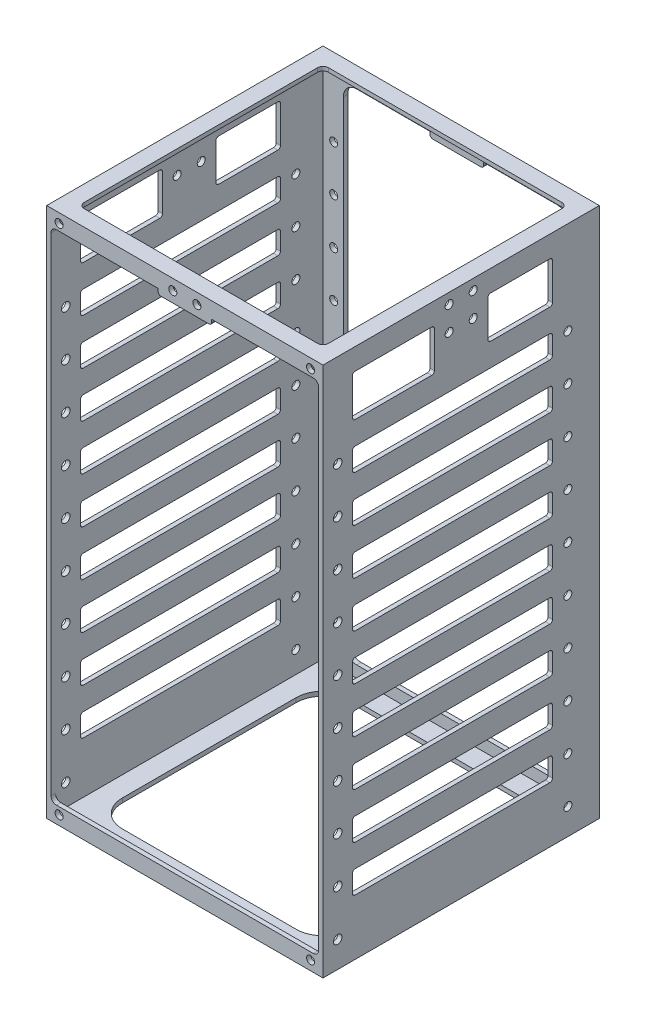
SolidWorks part; units mm, degrees
material "5052-H32"
ref_plane "Front Plane" through (0, 0, 0) normal (0, 0, 1) x (1, 0, 0)
ref_plane "Top Plane" through (0, 0, 0) normal (0, 1, 0) x (1, 0, 0)
ref_plane "Right Plane" through (0, 0, 0) normal (1, 0, 0) x (0, 0, -1)
sketch "Sketch1" plane through (0, 0, 0) normal (0, 1, 0) x (1, 0, 0)
  line L1 (-51.63, -51.63) -> (51.63, -51.63)
  line L2 (-51.63, -51.63) -> (-51.63, 51.63)
  line L3 (-51.63, 51.63) -> (51.63, 51.63)
  line L4 (51.63, -51.63) -> (51.63, 51.63)
  line L5 (-51.63, -51.63) -> (51.63, 51.63) construction
  line L6 (-51.63, 51.63) -> (51.63, -51.63) construction
  line L7 (-32.5, -42.5) -> (32.5, -42.5)
  line L8 (-42.5, -32.5) -> (-42.5, 32.5)
  line L9 (-32.5, 42.5) -> (32.5, 42.5)
  line L10 (42.5, -32.5) -> (42.5, 32.5)
  line L11 (-42.5, -42.5) -> (42.5, 42.5) construction
  line L12 (-42.5, 42.5) -> (42.5, -42.5) construction
  arc A0 (32.5, -42.5) -> (42.5, -32.5) centre (32.5, -32.5) ccw
  arc A1 (32.5, 42.5) -> (42.5, 32.5) centre (32.5, 32.5) cw
  arc A2 (-42.5, 32.5) -> (-32.5, 42.5) centre (-32.5, 32.5) cw
  arc A3 (-32.5, -42.5) -> (-42.5, -32.5) centre (-32.5, -32.5) cw
  point P0 (0, 0)
  point P6 (0, 0)
  dimension "D3" = 10
  dimension "D1" = 103.26
  dimension "D2" = 42.5
extrude "Boss-Extrude2" add sketch "Sketch1" along normal blind 1.63 contours A3 L7 A0 L10 A1 L9 A2 L8 | L2 L1 L4 L3 region at (0, 0, 0)
sketch "Sketch3" plane through (0, 1.63, 0) normal (0, 1, 0) x (1, 0, 0)
  line L1 (-51.63, -51.63) -> (51.63, -51.63)
  line L2 (-51.63, -51.63) -> (-51.63, 51.63)
  line L3 (-51.63, 51.63) -> (51.63, 51.63)
  line L4 (51.63, -51.63) -> (51.63, 51.63)
  line L5 (-51.63, -51.63) -> (51.63, 51.63) construction
  line L6 (-51.63, 51.63) -> (51.63, -51.63) construction
  line L7 (-50, -50) -> (50, -50)
  line L8 (-50, -50) -> (-50, 50)
  line L9 (-50, 50) -> (50, 50)
  line L10 (50, -50) -> (50, 50)
  line L11 (-50, -50) -> (50, 50) construction
  line L12 (-50, 50) -> (50, -50) construction
  point P0 (0, 0)
  point P7 (0, 0)
  dimension "D1" = 100
extrude "Boss-Extrude3" add sketch "Sketch3" along normal blind 196.74 contours L8 L7 L10 L9 | L2 L3 L4 L1
sketch "Sketch4" plane through (0, 0, -51.63) normal (0, 0, 1) x (1, 0, 0)
  line L0 (-51.63, 0) -> (51.63, 0) construction
  line L1 (-37.38, 6) -> (37.38, 6)
  line L2 (-42.38, 11) -> (-42.38, 187.37)
  line L3 (-37.38, 192.37) -> (37.38, 192.37)
  line L4 (42.38, 11) -> (42.38, 187.37)
  line L5 (-42.38, 6) -> (42.38, 192.37) construction
  line L6 (-42.38, 192.37) -> (42.38, 6) construction
  line L7 (51.63, 198.37) -> (51.63, 0) construction
  line L8 (-50, 198.37) -> (50, 198.37) construction
  line L9 (-51.63, 198.37) -> (-51.63, 0) construction
  arc A0 (-37.38, 6) -> (-42.38, 11) centre (-37.38, 11) cw
  arc A1 (37.38, 6) -> (42.38, 11) centre (37.38, 11) ccw
  arc A2 (37.38, 192.37) -> (42.38, 187.37) centre (37.38, 187.37) cw
  arc A3 (-42.38, 187.37) -> (-37.38, 192.37) centre (-37.38, 187.37) cw
  point P0 (0, 99.185)
  dimension "D5" = 5
  dimension "D1" = 6
  dimension "D2" = 9.25
  dimension "D3" = 6
  dimension "D4" = 9.25
extrude "Cut-Extrude1" cut sketch "Sketch4" along normal up to surface (1.63 mm away) up to face at (0, 100, -50)
sketch "Sketch5" plane through (0, 0, 51.63) normal (0, 0, 1) x (1, 0, 0)
  line L0 (-51.63, 198.37) -> (51.63, 198.37) construction
  line L1 (-48, 6.13) -> (48, 6.13)
  line L2 (-50, 8.13) -> (-50, 190.37)
  line L3 (-48, 192.37) -> (48, 192.37)
  line L4 (50, 8.13) -> (50, 190.37)
  line L5 (-50, 6.13) -> (50, 192.37) construction
  line L6 (-50, 192.37) -> (50, 6.13) construction
  line L7 (-51.63, 1.63) -> (51.63, 1.63) construction
  line L8 (-51.63, 198.37) -> (-51.63, 0) construction
  line L9 (51.63, 198.37) -> (51.63, 0) construction
  arc A0 (48, 6.13) -> (50, 8.13) centre (48, 8.13) ccw
  arc A1 (-48, 6.13) -> (-50, 8.13) centre (-48, 8.13) cw
  arc A2 (48, 192.37) -> (50, 190.37) centre (48, 190.37) cw
  arc A3 (-50, 190.37) -> (-48, 192.37) centre (-48, 190.37) cw
  point P0 (0, 99.25)
  dimension "D1" = 6
  dimension "D5" = 2
  dimension "D2" = 4.5
  dimension "D3" = 1.63
  dimension "D4" = 1.63
sketch "Sketch6" plane through (51.63, 0, 0) normal (1, 0, 0) x (0, 0, -1)
  line L0 (-51.63, 6.13) -> (-51.63, 192.37) construction
  line L2 (-51.63, 0) -> (51.63, 0) construction
  circle A0 centre (-46.13, 9.75) radius 1.6
  circle A1 centre (39.87, 9.75) radius 1.5
  circle A2 centre (-46.13, 26.85) radius 1.6
  circle A3 centre (39.87, 26.85) radius 1.5
  circle A4 centre (-46.13, 43.95) radius 1.6
  circle A5 centre (39.87, 43.95) radius 1.5
  circle A6 centre (-46.13, 61.05) radius 1.6
  circle A7 centre (39.87, 61.05) radius 1.5
  circle A8 centre (-46.13, 78.15) radius 1.6
  circle A9 centre (39.87, 78.15) radius 1.5
  circle A10 centre (-46.13, 95.25) radius 1.6
  circle A11 centre (39.87, 95.25) radius 1.5
  circle A12 centre (-46.13, 112.35) radius 1.6
  circle A13 centre (39.87, 112.35) radius 1.5
  circle A14 centre (-46.13, 129.45) radius 1.6
  circle A15 centre (39.87, 129.45) radius 1.5
  circle A16 centre (-46.13, 146.55) radius 1.6
  circle A17 centre (39.87, 146.55) radius 1.5
  circle A18 centre (-46.13, 163.65) radius 1.6
  circle A19 centre (39.87, 163.65) radius 1.5
  dimension "D4" = 3
  dimension "D5" = 3.2
  dimension "D1" = 5.5
  dimension "D2" = 86
  dimension "D3" = 9.75
  dimension "D7" = 17.1
  dimension "D9" = 17.1
  dimension "D6" = 9
  dimension "D8" = 2
extrude "Cut-Extrude2" cut sketch "Sketch6" against normal through all
extrude "Cut-Extrude3" cut sketch "Sketch5" against normal up to surface (1.63 mm away) up to face at (0, 100, 50)
sketch "Sketch7" plane through (51.63, 0, 0) normal (1, 0, 0) x (0, 0, -1)
  line L0 (-40.63, 38.95) -> (-40.63, 45.45)
  line L1 (-39.63, 20.85) -> (33.12, 20.85)
  line L2 (-40.63, 21.85) -> (-40.63, 28.35)
  line L3 (-39.63, 29.35) -> (33.12, 29.35)
  line L4 (34.12, 21.85) -> (34.12, 28.35)
  line L5 (-40.63, 20.85) -> (34.12, 29.35) construction
  line L6 (-40.63, 29.35) -> (34.12, 20.85) construction
  line L7 (-40.63, 158.65) -> (-40.63, 165.15)
  line L8 (-39.63, 37.95) -> (33.12, 37.95)
  line L9 (34.12, 38.95) -> (34.12, 45.45)
  line L10 (-39.63, 46.45) -> (33.12, 46.45)
  line L11 (-40.63, 56.05) -> (-40.63, 62.55)
  line L12 (-39.63, 55.05) -> (33.12, 55.05)
  line L13 (34.12, 56.05) -> (34.12, 62.55)
  line L14 (-39.63, 63.55) -> (33.12, 63.55)
  line L15 (-40.63, 73.15) -> (-40.63, 79.65)
  line L16 (-39.63, 72.15) -> (33.12, 72.15)
  line L17 (34.12, 73.15) -> (34.12, 79.65)
  line L18 (-39.63, 80.65) -> (33.12, 80.65)
  line L19 (-40.63, 90.25) -> (-40.63, 96.75)
  line L20 (-39.63, 89.25) -> (33.12, 89.25)
  line L21 (34.12, 90.25) -> (34.12, 96.75)
  line L22 (-39.63, 97.75) -> (33.12, 97.75)
  line L23 (-40.63, 107.35) -> (-40.63, 113.85)
  line L24 (-39.63, 106.35) -> (33.12, 106.35)
  line L25 (34.12, 107.35) -> (34.12, 113.85)
  line L26 (-39.63, 114.85) -> (33.12, 114.85)
  line L27 (-40.63, 124.45) -> (-40.63, 130.95)
  line L28 (-39.63, 123.45) -> (33.12, 123.45)
  line L29 (34.12, 124.45) -> (34.12, 130.95)
  line L30 (-39.63, 131.95) -> (33.12, 131.95)
  line L31 (-40.63, 141.55) -> (-40.63, 148.05)
  line L32 (-39.63, 140.55) -> (33.12, 140.55)
  line L33 (34.12, 141.55) -> (34.12, 148.05)
  line L34 (-39.63, 149.05) -> (33.12, 149.05)
  line L35 (-39.63, 157.65) -> (33.12, 157.65)
  line L36 (34.12, 158.65) -> (34.12, 165.15)
  line L37 (-39.63, 166.15) -> (33.12, 166.15)
  line L38 (-40.63, 141.55) -> (-40.63, 158.65) construction
  circle A0 centre (-46.13, 9.75) radius 1.6 construction
  arc A1 (33.12, 29.35) -> (34.12, 28.35) centre (33.12, 28.35) cw
  arc A2 (33.12, 20.85) -> (34.12, 21.85) centre (33.12, 21.85) ccw
  arc A3 (-39.63, 20.85) -> (-40.63, 21.85) centre (-39.63, 21.85) cw
  arc A4 (-40.63, 28.35) -> (-39.63, 29.35) centre (-39.63, 28.35) cw
  arc A5 (-40.63, 45.45) -> (-39.63, 46.45) centre (-39.63, 45.45) cw
  arc A6 (-39.63, 37.95) -> (-40.63, 38.95) centre (-39.63, 38.95) cw
  arc A7 (33.12, 37.95) -> (34.12, 38.95) centre (33.12, 38.95) ccw
  arc A8 (33.12, 46.45) -> (34.12, 45.45) centre (33.12, 45.45) cw
  arc A9 (-40.63, 62.55) -> (-39.63, 63.55) centre (-39.63, 62.55) cw
  arc A10 (-39.63, 55.05) -> (-40.63, 56.05) centre (-39.63, 56.05) cw
  arc A11 (33.12, 55.05) -> (34.12, 56.05) centre (33.12, 56.05) ccw
  arc A12 (33.12, 63.55) -> (34.12, 62.55) centre (33.12, 62.55) cw
  arc A13 (-40.63, 79.65) -> (-39.63, 80.65) centre (-39.63, 79.65) cw
  arc A14 (-39.63, 72.15) -> (-40.63, 73.15) centre (-39.63, 73.15) cw
  arc A15 (33.12, 72.15) -> (34.12, 73.15) centre (33.12, 73.15) ccw
  arc A16 (33.12, 80.65) -> (34.12, 79.65) centre (33.12, 79.65) cw
  arc A17 (-40.63, 96.75) -> (-39.63, 97.75) centre (-39.63, 96.75) cw
  arc A18 (-39.63, 89.25) -> (-40.63, 90.25) centre (-39.63, 90.25) cw
  arc A19 (33.12, 89.25) -> (34.12, 90.25) centre (33.12, 90.25) ccw
  arc A20 (33.12, 97.75) -> (34.12, 96.75) centre (33.12, 96.75) cw
  arc A21 (-40.63, 113.85) -> (-39.63, 114.85) centre (-39.63, 113.85) cw
  arc A22 (-39.63, 106.35) -> (-40.63, 107.35) centre (-39.63, 107.35) cw
  arc A23 (33.12, 106.35) -> (34.12, 107.35) centre (33.12, 107.35) ccw
  arc A24 (33.12, 114.85) -> (34.12, 113.85) centre (33.12, 113.85) cw
  arc A25 (-40.63, 130.95) -> (-39.63, 131.95) centre (-39.63, 130.95) cw
  arc A26 (-39.63, 123.45) -> (-40.63, 124.45) centre (-39.63, 124.45) cw
  arc A27 (33.12, 123.45) -> (34.12, 124.45) centre (33.12, 124.45) ccw
  arc A28 (33.12, 131.95) -> (34.12, 130.95) centre (33.12, 130.95) cw
  arc A29 (-40.63, 148.05) -> (-39.63, 149.05) centre (-39.63, 148.05) cw
  arc A30 (-39.63, 140.55) -> (-40.63, 141.55) centre (-39.63, 141.55) cw
  arc A31 (33.12, 140.55) -> (34.12, 141.55) centre (33.12, 141.55) ccw
  arc A32 (33.12, 149.05) -> (34.12, 148.05) centre (33.12, 148.05) cw
  arc A33 (-40.63, 165.15) -> (-39.63, 166.15) centre (-39.63, 165.15) cw
  arc A34 (-39.63, 157.65) -> (-40.63, 158.65) centre (-39.63, 158.65) cw
  circle A35 centre (39.87, 9.75) radius 1.5 construction
  arc A36 (33.12, 157.65) -> (34.12, 158.65) centre (33.12, 158.65) ccw
  arc A37 (33.12, 166.15) -> (34.12, 165.15) centre (33.12, 165.15) cw
  point P0 (-3.255, 25.1)
  dimension "D5" = 1
  dimension "D3" = 5.75
  dimension "D1" = 8.5
  dimension "D2" = 11.1
  dimension "D4" = 5.5
  dimension "D7" = 8.6
  dimension "D9" = 8.6
  dimension "D6" = 8
  dimension "D8" = 2
extrude "Cut-Extrude4" cut sketch "Sketch7" against normal through all
sketch "Sketch8" plane through (51.63, 0, 0) normal (1, 0, 0) x (0, 0, -1)
  line L7 (-51.63, 198.37) -> (51.63, 198.37) construction
  line L15 (-39.63, 190.37) -> (33.12, 190.37)
  line L16 (-40.63, 189.37) -> (-40.63, 175.75)
  line L17 (-39.63, 174.75) -> (33.12, 174.75)
  line L18 (34.12, 189.37) -> (34.12, 175.75)
  line L19 (33.12, 166.15) -> (-39.63, 166.15) construction
  arc A15 (33.12, 190.37) -> (34.12, 189.37) centre (33.12, 189.37) cw
  arc A16 (33.12, 174.75) -> (34.12, 175.75) centre (33.12, 175.75) ccw
  arc A17 (-40.63, 175.75) -> (-39.63, 174.75) centre (-39.63, 175.75) ccw
  arc A18 (-39.63, 190.37) -> (-40.63, 189.37) centre (-39.63, 189.37) ccw
  circle A19 centre (-46.13, 163.65) radius 1.6 construction
  circle A20 centre (39.87, 163.65) radius 1.5 construction
  point P0 (-2.625, 162.85)
  dimension "D6" = 1
  dimension "D2" = 8.6
  dimension "D8" = 8
  dimension "D9" = 5.5
  dimension "D10" = 5.75
extrude "Cut-Extrude5" cut sketch "Sketch8" against normal through all
sketch "Sketch15" plane through (51.63, 0, 0) normal (1, 0, 0) x (0, 0, -1)
  line L0 (-50, 198.37) -> (-50, 190.37) construction
  line L7 (33.12, 190.37) -> (-39.63, 190.37) construction
  line L8 (-10, 190.37) -> (10, 190.37)
  line L9 (-10, 190.37) -> (-10, 174.75)
  line L10 (-10, 174.75) -> (10, 174.75)
  line L11 (10, 190.37) -> (10, 174.75)
  line L12 (-39.63, 174.75) -> (33.12, 174.75) construction
  dimension "D1" = 20
  dimension "D2" = 40
extrude "Boss-Extrude4" add sketch "Sketch15" against normal up to surface (1.63 mm away) up to face at (50, 182.56, 3.255)
sketch "Sketch16" plane through (-51.63, 0, 0) normal (-1, 0, 0) x (0, 0, 1)
  line L7 (-10, 190.37) -> (10, 190.37)
  line L8 (-10, 190.37) -> (-10, 174.75)
  line L9 (-10, 174.75) -> (10, 174.75)
  line L10 (10, 190.37) -> (10, 174.75)
extrude "Boss-Extrude5" add sketch "Sketch16" against normal up to surface (1.63 mm away) up to face at (-50, 182.56, 3.255)
sketch "Sketch9" plane through (51.63, 0, 0) normal (1, 0, 0) x (0, 0, -1)
  line L0 (-51.63, 198.37) -> (51.63, 198.37) construction
  line L2 (-11.0428, 189.87) -> (9.2919, 189.87) construction
  line L3 (-50, 198.37) -> (-50, 190.37) construction
  circle A0 centre (-4.5, 194.37) radius 1.5
  circle A1 centre (4.5, 194.37) radius 1.5
  circle A2 centre (4.5, 185.37) radius 1.5
  circle A3 centre (-4.5, 185.37) radius 1.5
  dimension "D1" = 3
  dimension "D3" = 9
  dimension "D5" = 3
  dimension "D2" = 4
  dimension "D4" = 45.5
  dimension "D6" = 4.5
extrude "Cut-Extrude6" cut sketch "Sketch9" against normal through all
fillet "Fillet1" radius 1 8 edges at (-50.815, 174.75, 10) (-50.815, 190.37, 10) (-50.815, 190.37, -10) (-50.815, 174.75, -10) (50.815, 190.37, 10) (50.815, 174.75, 10) (50.815, 174.75, -10) (50.815, 190.37, -10)
sketch "Sketch18" plane through (0, 0, -51.63) normal (0, 0, -1) x (-1, 0, 0)
  line L0 (-37.38, 192.37) -> (37.38, 192.37) construction
  line L1 (-10, 192.37) -> (10, 192.37)
  line L2 (-10, 192.37) -> (-10, 191.37)
  line L3 (-9, 190.37) -> (9, 190.37)
  line L4 (10, 192.37) -> (10, 191.37)
  line L6 (-50, 198.37) -> (-50, 1.63) construction
  arc A0 (9, 190.37) -> (10, 191.37) centre (9, 191.37) ccw
  arc A1 (-10, 191.37) -> (-9, 190.37) centre (-9, 191.37) ccw
  point P4 (-10, 191.87)
  dimension "D3" = 1
  dimension "D1" = 2
  dimension "D2" = 20
  dimension "D4" = 40
extrude "Boss-Extrude7" add sketch "Sketch18" against normal up to surface (1.63 mm away) up to face at (0, 99.185, -50)
sketch "Sketch17" plane through (0, 0, 51.63) normal (0, 0, 1) x (1, 0, 0)
  line L0 (48, 192.37) -> (-48, 192.37) construction
  line L1 (-10, 192.37) -> (10, 192.37)
  line L2 (-10, 192.37) -> (-10, 191.37)
  line L3 (-9, 190.37) -> (9, 190.37)
  line L4 (10, 192.37) -> (10, 191.37)
  line L5 (-50, 198.37) -> (-50, 190.37) construction
  arc A0 (9, 190.37) -> (10, 191.37) centre (9, 191.37) ccw
  arc A1 (-10, 191.37) -> (-9, 190.37) centre (-9, 191.37) ccw
  dimension "D4" = 1
  dimension "D1" = 20
  dimension "D2" = 40
  dimension "D3" = 2
extrude "Boss-Extrude6" add sketch "Sketch17" against normal up to surface (1.63 mm away) up to face at (0, 193.8414, 50)
sketch "Sketch19" plane through (0, 0, 51.63) normal (0, 0, 1) x (1, 0, 0)
  line L0 (0, 198.37) -> (0, 190.37) construction
  line L1 (-9, 190.37) -> (9, 190.37) construction
  line L3 (-51.63, 198.37) -> (51.63, 198.37) construction
  circle A0 centre (-4.5, 194.37) radius 1.5
  circle A1 centre (4.5, 194.37) radius 1.5
  dimension "D1" = 3
  dimension "D2" = 4
  dimension "D3" = 4.5
extrude "Cut-Extrude7" cut sketch "Sketch19" against normal through all
sketch "Sketch20" plane through (0, 0, 51.63) normal (0, 0, 1) x (1, 0, 0)
  line L1 (-51.63, 0) -> (51.63, 0) construction
  line L2 (0, 198.37) -> (0, 0) construction
  line L3 (-51.63, 198.37) -> (51.63, 198.37) construction
  line L4 (-50, 198.37) -> (-50, 190.37) construction
  line L5 (-50, 8.13) -> (-50, 1.63) construction
  circle A0 centre (-46.98, 3.5) radius 1.5
  circle A1 centre (-46.98, 194.87) radius 1.5
  circle A2 centre (46.98, 3.5) radius 1.5
  circle A3 centre (46.98, 194.87) radius 1.5
  dimension "D1" = 3
  dimension "D4" = 3
  dimension "D2" = 3.02
  dimension "D3" = 3.5
  dimension "D5" = 3.02
  dimension "D6" = 3.5
extrude "Cut-Extrude8" cut sketch "Sketch20" against normal up to surface (1.63 mm away) up to face at (-6, 194.37, 50)
sketch "Sketch23" plane through (0, 0, -51.63) normal (0, 0, -1) x (-1, 0, 0)
  line L0 (-51.63, 198.37) -> (-51.63, 0) construction
  line L1 (51.63, 0) -> (-51.63, 0) construction
  line L2 (0, 198.37) -> (0, 0) construction
  line L3 (51.63, 198.37) -> (-51.63, 198.37) construction
  circle A0 centre (-46, 17.05) radius 1.5
  circle A2 centre (-46, 34.15) radius 1.5
  circle A3 centre (-46, 51.25) radius 1.5
  circle A4 centre (-46, 68.35) radius 1.5
  circle A5 centre (-46, 85.45) radius 1.5
  circle A6 centre (-46, 102.55) radius 1.5
  circle A7 centre (-46, 119.65) radius 1.5
  circle A8 centre (-46, 136.75) radius 1.5
  circle A9 centre (-46, 153.85) radius 1.5
  circle A10 centre (-46, 170.95) radius 1.5
  circle A11 centre (46, 170.95) radius 1.5
  circle A12 centre (46, 153.85) radius 1.5
  circle A13 centre (46, 136.75) radius 1.5
  circle A14 centre (46, 119.65) radius 1.5
  circle A15 centre (46, 102.55) radius 1.5
  circle A16 centre (46, 85.45) radius 1.5
  circle A17 centre (46, 68.35) radius 1.5
  circle A18 centre (46, 51.25) radius 1.5
  circle A19 centre (46, 34.15) radius 1.5
  circle A20 centre (46, 17.05) radius 1.5
  dimension "D1" = 3
  dimension "D2" = 5.63
  dimension "D3" = 17.05
  dimension "D5" = 17.1
  dimension "D4" = 10
extrude "Cut-Extrude10" cut sketch "Sketch23" against normal up to surface (1.63 mm away) up to face at (-6, 194.37, -50)
sketch "Sketch25" plane through (0, 198.37, 0) normal (0, 1, 0) x (1, 0, 0)
  line L1 (-50, -50) -> (50, -50)
  line L2 (-50, -50) -> (-50, 50)
  line L3 (-50, 50) -> (50, 50)
  line L4 (50, -50) -> (50, 50)
  line L5 (-50, -50) -> (50, 50) construction
  line L6 (-50, 50) -> (50, -50) construction
  point P0 (0, 0)
extrude "Boss-Extrude8" add sketch "Sketch25" against normal blind 1.5
sketch "Sketch26" plane through (0, 198.37, 0) normal (0, 1, 0) x (1, 0, 0)
  line L0 (-51.63, -51.63) -> (-51.63, 51.63) construction
  line L1 (-43.63, -45.63) -> (43.63, -45.63)
  line L2 (-45.63, -43.63) -> (-45.63, 43.63)
  line L3 (-43.63, 45.63) -> (43.63, 45.63)
  line L4 (45.63, -43.63) -> (45.63, 43.63)
  line L5 (-45.63, -45.63) -> (45.63, 45.63) construction
  line L6 (-45.63, 45.63) -> (45.63, -45.63) construction
  arc A0 (-45.63, 43.63) -> (-43.63, 45.63) centre (-43.63, 43.63) cw
  arc A1 (43.63, 45.63) -> (45.63, 43.63) centre (43.63, 43.63) cw
  arc A2 (43.63, -45.63) -> (45.63, -43.63) centre (43.63, -43.63) ccw
  arc A3 (-43.63, -45.63) -> (-45.63, -43.63) centre (-43.63, -43.63) cw
  point P0 (0, 0)
  dimension "D2" = 2
  dimension "D1" = 6
extrude "Cut-Extrude11" cut sketch "Sketch26" against normal up to surface (1.5 mm away) up to face at (0, 196.87, 0)
equation "\"D2@Sketch4\"=\"D4@Sketch4\""
equation "\"D4@Sketch5\"=\"D3@Sketch5\""
